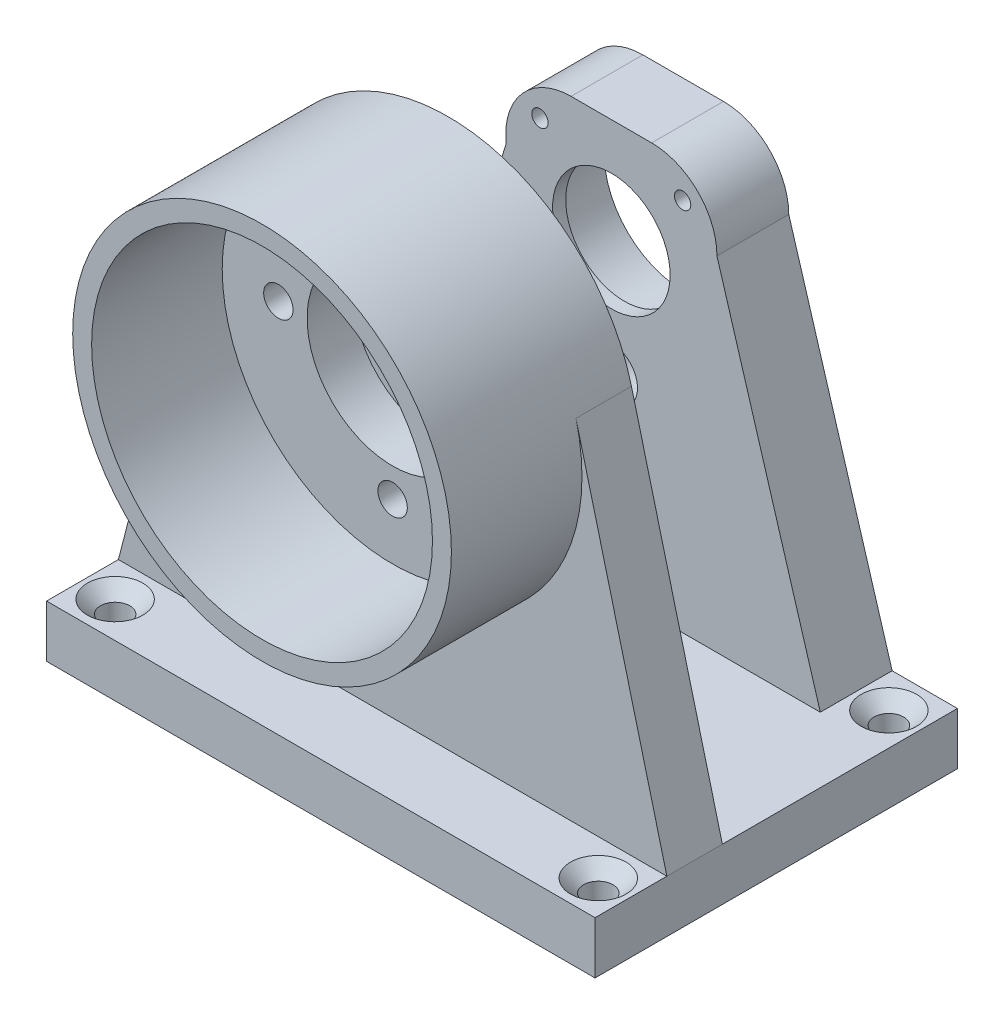
SolidWorks part; units mm, degrees
material "PET"
ref_plane "Piano frontale" through (0, 0, 0) normal (0, 0, 1) x (1, 0, 0)
ref_plane "Piano superiore" through (0, 0, 0) normal (0, 1, 0) x (1, 0, 0)
ref_plane "Piano destro" through (0, 0, 0) normal (1, 0, 0) x (0, 0, -1)
sketch "Schizzo1" plane through (0, 0, 0) normal (0, 0, 1) x (1, 0, 0)
  line L0 (-16.1, 0) -> (0, 0) construction
  line L1 (-6.1713, 16.1) -> (6.1713, 16.1)
  line L3 (-17, -54.5) -> (17, -54.5)
  line L5 (0, 0) -> (16.1, 0) construction
  line L7 (-17, -54.5) -> (-42, -54.5)
  line L11 (17, -54.5) -> (42, -54.5)
  line L16 (42, -54.5) -> (42, -46.5)
  line L18 (-42, -54.5) -> (-42, -46.5)
  line L20 (42, -46.5) -> (32, -46.5)
  line L21 (32, -46.5) -> (16.1713, 6.1)
  line L22 (-42, -46.5) -> (-32, -46.5)
  line L23 (-32, -46.5) -> (-16.1, 4.9079)
  circle A0 centre (0, 0) radius 12.1
  arc A1 (16.1713, 6.1) -> (6.1713, 16.1) centre (6.1713, 6.1) ccw
  arc A2 (-16.1, 4.9079) -> (-6.1713, 16.1) centre (-6.1713, 6.1) cw
  point P13 (0, -54.5)
  point P14 (0, 16.1)
  dimension "D1" = 24.2
  dimension "D3" = 25
  dimension "D4" = 10
  dimension "D7" = 8
  dimension "D2" = 16.1
  dimension "D5" = 54.5
  dimension "D6" = 34
  dimension "D8" = 10
  dimension "D9" = 10
extrude "Estrusione-Estrusione1" add sketch "Schizzo1" along normal blind 11
sketch "Schizzo2" plane through (0, 0, 11) normal (0, 0, 1) x (1, 0, 0)
  circle A0 centre (0, 0) radius 9
  circle A1 centre (0, 0) radius 12.1
  dimension "D1" = 18
extrude "Estrusione-Estrusione2" add sketch "Schizzo2" against normal blind 2
sketch "Schizzo3" plane through (0, -46.5, 0) normal (0, 1, 0) x (1, 0, 0)
  line L0 (32, -11) -> (42, 0) construction
  line L1 (-42, -11) -> (-32, 0) construction
  circle A0 centre (37, -5.5) radius 2.25
  circle A1 centre (-37, -5.5) radius 2.25
  dimension "D1" = 4.5
extrude "Taglio-Estrusione1" cut sketch "Schizzo3" against normal through all
chamfer "Smusso1" distance 2 angle 45 2 edges at (-37, -46.5, 7.75) (37, -46.5, 7.75)
sketch "Schizzo4" plane through (0, 0, 0) normal (0, 0, -1) x (-1, 0, 0)
  line L0 (-8.5791, 8.5329) -> (-13.2424, 13.1711) construction
  line L1 (8.6056, 8.5061) -> (13.2834, 13.1299) construction
  line L2 (0, -12.1) -> (0, -18.6772) construction
  arc A0 (-6.1713, 16.1) -> (-16.1713, 6.1) centre (-6.1713, 6.1) ccw construction
  arc A1 (16.1, 4.9079) -> (6.1713, 16.1) centre (6.1713, 6.1) ccw construction
  circle A2 centre (0, 0) radius 12.1 construction
  circle A3 centre (0, 0) radius 12.1 construction
  circle A4 centre (-10.9107, 10.852) radius 1.25
  circle A5 centre (10.9445, 10.818) radius 1.25
  circle A6 centre (0, -15.3886) radius 1.25
  dimension "D1" = 2.5
extrude "Taglio-Estrusione2" cut sketch "Schizzo4" against normal through all
sketch "Schizzo5" plane through (0, 0, 11) normal (0, 0, 1) x (1, 0, 0)
  line L0 (-42, -54.5) -> (42, -54.5) construction
  line L1 (-42, -46.5) -> (42, -46.5)
  line L2 (-42, -46.5) -> (-42, -54.5)
  line L3 (-42, -54.5) -> (42, -54.5)
  line L4 (42, -46.5) -> (42, -54.5)
  line L5 (42, -54.5) -> (42, -46.5) construction
extrude "Estrusione-Estrusione3" add sketch "Schizzo5" along normal blind 25
sketch "Schizzo6" plane through (0, 0, 36) normal (0, 0, 1) x (1, 0, 0)
  line L0 (-42, -46.5) -> (-28.0737, 7.2709)
  line L1 (42, -46.5) -> (28.0737, 7.2709)
  line L3 (-42, -46.5) -> (42, -46.5)
  line L4 (-42, -46.5) -> (-42, -54.5)
  line L5 (-42, -54.5) -> (42, -54.5)
  line L6 (42, -46.5) -> (42, -54.5)
  circle A0 centre (0, 0) radius 29
  circle A1 centre (0, 0) radius 6
  circle A2 centre (0, 0) radius 17.5
  circle A3 centre (0, 17.5) radius 2.25
  circle A4 centre (17.5, 0) radius 2.25
  circle A5 centre (0, -17.5) radius 2.25
  circle A6 centre (-17.5, 0) radius 2.25
  line M5 (-42, -46.5) -> (-42, -54.5)
  line M6 (-42, -54.5) -> (42, -54.5)
  line M7 (42, -54.5) -> (42, -46.5)
  line M8 (42, -46.5) -> (-42, -46.5)
  dimension "D1" = 58
  dimension "D2" = 12
  dimension "D3" = 35
  dimension "D4" = 4.5
extrude "Estrusione-Estrusione4" add sketch "Schizzo6" along normal blind 1.5 contours A0 L0 L1 M8 | A0 A6 A2 A3 A4 A5 | A6 A2 A5 A4 A3 A1 | M8 M5 M6 M7 region at (0, -32.4524, 36) region at (0, -50.5, 36) region at (0, 28.1798, 36) region at (14.7591, 0, 36)
sketch "Schizzo7" plane through (0, 0, 37.5) normal (0, 0, 1) x (1, 0, 0)
  line L5 (42, -46.5) -> (28.0737, 7.2709)
  line L6 (-28.0737, 7.2709) -> (-42, -46.5)
  line L7 (-42, -46.5) -> (-42, -54.5)
  line L8 (-42, -54.5) -> (42, -54.5)
  line L9 (42, -54.5) -> (42, -46.5)
  line L10 (42, -46.5) -> (28.0737, 7.2709)
  line L11 (-28.0737, 7.2709) -> (-42, -46.5)
  line L12 (-42, -46.5) -> (-42, -54.5)
  line L13 (-42, -54.5) -> (42, -54.5)
  line L14 (42, -54.5) -> (42, -46.5)
  circle A0 centre (0, -17.5) radius 2.25 construction
  arc A1 (28.0737, 7.2709) -> (-28.0737, 7.2709) centre (0, 0) ccw
  arc A2 (28.0737, 7.2709) -> (-28.0737, 7.2709) centre (0, 0) ccw
  circle A3 centre (17.5, 0) radius 2.25 construction
  circle A4 centre (0, 17.5) radius 2.25 construction
  circle A5 centre (-17.5, 0) radius 2.25 construction
  circle A6 centre (0, -17.5) radius 2.25
  circle A7 centre (17.5, 0) radius 2.25
  circle A8 centre (0, 17.5) radius 2.25
  circle A9 centre (-17.5, 0) radius 2.25
  circle A10 centre (0, 0) radius 13.1
  dimension "D2" = 26.2
  dimension "D1" = 0
extrude "Estrusione-Estrusione5" add sketch "Schizzo7" along normal blind 7
sketch "Schizzo8" plane through (0, 0, 44.5) normal (0, 0, 1) x (1, 0, 0)
  circle A0 centre (0, 0) radius 26.1
  circle A1 centre (0, 0) radius 29
  dimension "D1" = 52.2
extrude "Estrusione-Estrusione6" add sketch "Schizzo8" along normal blind 20
sketch "Schizzo9" plane through (0, 0, 0) normal (0, 0, -1) x (-1, 0, 0)
  circle A0 centre (0, -17.5) radius 2.25 construction
  circle A1 centre (0, -17.5) radius 2.25
  circle A2 centre (0, -17.5) radius 4
  circle M5 centre (0, -15.3886) radius 1.25
  dimension "D1" = 8
extrude "Taglio-Estrusione4" cut sketch "Schizzo9" against normal up to next contours A2 A1 M5 | A1 M5 | A1 M5 | A1 M5 region at (0, -17.7978, 0) region at (0, -15.9034, 0) region at (0, -14.8544, 0) region at (3.8869, -17.5, 0)
sketch "Schizzo10" plane through (0, 0, 44.5) normal (0, 0, 1) x (1, 0, 0)
  line L0 (42, -54.5) -> (42, -46.5) construction
  line L1 (-42, -46.5) -> (42, -46.5)
  line L2 (-42, -46.5) -> (-42, -54.5)
  line L3 (-42, -54.5) -> (42, -54.5)
  line L4 (-32, -46.5) -> (32, -46.5)
  line L5 (32, -46.5) -> (16.1713, 6.1)
  line L6 (6.1713, 16.1) -> (-6.1713, 16.1)
  line L7 (-16.1, 4.9079) -> (-32, -46.5)
  line L8 (-32, -46.5) -> (32, -46.5)
  line L9 (32, -46.5) -> (16.1713, 6.1)
  line L10 (6.1713, 16.1) -> (-6.1713, 16.1)
  line L11 (-16.1, 4.9079) -> (-32, -46.5)
  line L12 (42, -46.5) -> (42, -54.5)
  line L13 (-42, -54.5) -> (42, -54.5) construction
  arc A2 (16.1713, 6.1) -> (6.1713, 16.1) centre (6.1713, 6.1) ccw
  arc A3 (-6.1713, 16.1) -> (-16.1, 4.9079) centre (-6.1713, 6.1) ccw
  arc A4 (16.1713, 6.1) -> (6.1713, 16.1) centre (6.1713, 6.1) ccw
  arc A5 (-6.1713, 16.1) -> (-16.1, 4.9079) centre (-6.1713, 6.1) ccw
  line M9 (-42, -46.5) -> (-42, -54.5)
  line M10 (-42, -54.5) -> (42, -54.5)
  line M11 (42, -54.5) -> (42, -46.5)
  dimension "D1" = 0
extrude "Estrusione-Estrusione7" add sketch "Schizzo10" along normal blind 11 contours L1 M9 M10 M11 region at (0, -50.5, 44.5)
sketch "Schizzo11" plane through (0, -46.5, 0) normal (0, 1, 0) x (1, 0, 0)
  line L0 (-42, -50) -> (-37, -50)
  line L1 (-42, -55.5) -> (-42, -44.5) construction
  line L2 (42, -50) -> (37, -50)
  line L3 (42, -55.5) -> (42, -44.5) construction
  circle A0 centre (-37, -50) radius 2.25
  circle A1 centre (37, -50) radius 2.25
  circle A2 centre (37, -5.5) radius 2.25 construction
  dimension "D1" = 5
extrude "Taglio-Estrusione5" cut sketch "Schizzo11" against normal through all contours A0 | A1 region at (-37, -46.5, 52.1864) region at (34.8136, -46.5, 50)
chamfer "Smusso2" distance 2 angle 45 2 edges at (-37, -46.5, 52.25) (37, -46.5, 52.25)
